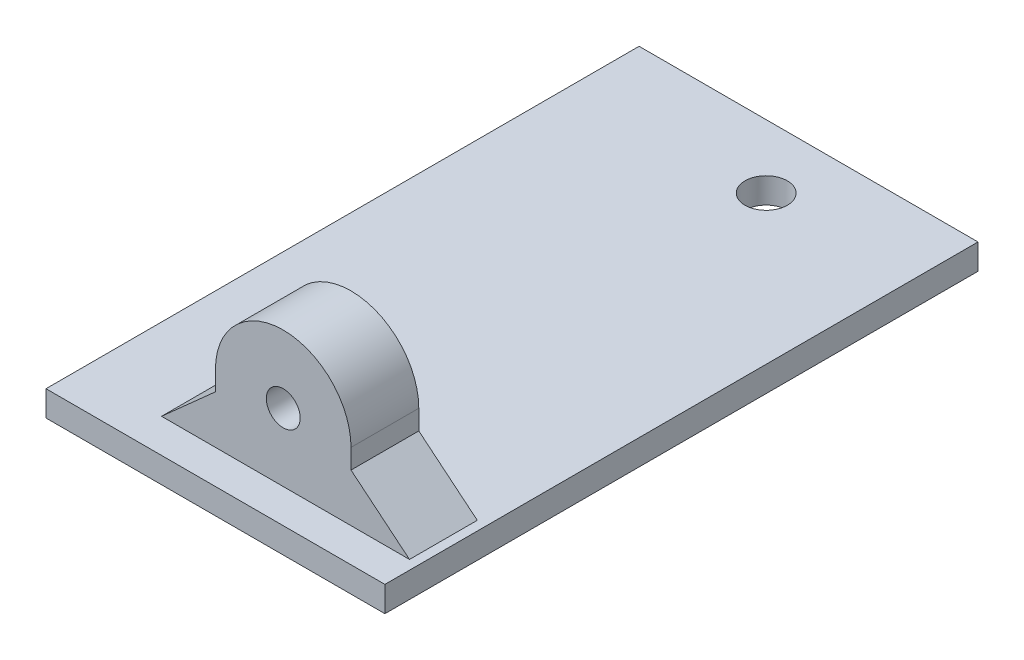
SolidWorks part; units mm, degrees
ref_plane "Front Plane" through (0, 0, 0) normal (0, 0, 1) x (1, 0, 0)
ref_plane "Top Plane" through (0, 0, 0) normal (0, 1, 0) x (1, 0, 0)
ref_plane "Right Plane" through (0, 0, 0) normal (1, 0, 0) x (0, 0, -1)
sketch "Sketch1" plane through (0, 0, 0) normal (0, 1, 0) x (1, 0, 0)
  line L1 (-40, -30) -> (40, -30)
  line L2 (-40, -30) -> (-40, 30)
  line L3 (-40, 30) -> (40, 30)
  line L4 (40, -30) -> (40, 30)
  line L5 (0, 30) -> (0, -30) construction
  line L6 (-40, 0) -> (40, 0) construction
  point P0 (0, 0)
  dimension "D1" = 60
  dimension "D2" = 80
extrude "Boss-Extrude1" add sketch "Sketch1" along normal blind 3
sketch "Sketch3" plane through (0, 3, 0) normal (0, 1, 0) x (1, 0, 0)
  line L1 (-26.5, -22.5) -> (22.5, -22.5)
  line L2 (-26.5, -22.5) -> (-26.5, 22.5)
  line L3 (-26.5, 22.5) -> (22.5, 22.5)
  line L4 (22.5, -22.5) -> (22.5, 22.5)
  line L5 (-2, 22.5) -> (-2, -22.5) construction
  line L6 (-26.5, 0) -> (22.5, 0) construction
  circle A0 centre (-26.5, 22.5) radius 2.5
  circle A1 centre (22.5, 22.5) radius 2.5
  circle A2 centre (22.5, -22.5) radius 2.5
  circle A3 centre (-26.5, -22.5) radius 2.5
  point P9 (-2, 0)
  dimension "D1" = 5
  dimension "D2" = 49
  dimension "D3" = 45
  dimension "D4" = 22.5
extrude "Cut-Extrude1" cut sketch "Sketch3" against normal blind 10 contours L3 A0 L2 | L2 A0 L3 | L4 A1 L3 | L3 A1 L4 | L1 A2 L4 | L4 A2 L1 | L2 A3 L1 | L1 A3 L2 region at (-25.439, 3, 21.439) region at (-26.8537, 3, 22.8537) region at (21.439, 3, 21.439) region at (22.8537, 3, 22.8537) region at (-26.8537, 3, -22.8537) region at (-25.439, 3, -21.439) region at (21.439, 3, -21.439) region at (22.8537, 3, -22.8537)
sketch "Sketch9" plane through (0, 3, 0) normal (0, 1, 0) x (1, 0, 0)
  line L1 (-33, 8.2578) -> (-17, 8.2578)
  line L2 (-33, 8.2578) -> (-33, 0.2578)
  line L3 (-33, 0.2578) -> (-17, 0.2578)
  line L4 (-17, 8.2578) -> (-17, 0.2578)
  line L5 (-25, 0.2578) -> (-25, 8.2578) construction
  line L6 (-33, 4.2578) -> (-17, 4.2578) construction
  point P0 (-25, 4.2578)
  dimension "D1" = 8
  dimension "D2" = 16
  dimension "D4" = 25
extrude "Boss-Extrude3" add sketch "Sketch9" along normal blind 50
sketch "Sketch10" plane through (0, 0, -0.2578) normal (0, 0, 1) x (1, 0, 0)
  line L0 (-33, 53) -> (-17, 53) construction
  line L1 (-33, 53) -> (-33, 3) construction
  line L2 (-17, 53) -> (-17, 3) construction
  line L3 (-33, 45) -> (-33, 53)
  line L4 (-33, 53) -> (-17, 53)
  line L5 (-17, 53) -> (-17, 45)
  circle A0 centre (-25, 45) radius 8
  line M2 (-17, 3) -> (-17, 53)
  line M3 (-17, 53) -> (-33, 53)
  line M4 (-33, 53) -> (-33, 3)
extrude "Cut-Extrude3" cut sketch "Sketch10" against normal blind 50 contours A0 M2 M3 | A0 L4 M4 region at (-31.2131, 51.2131, -0.2578) region at (-18.7869, 51.2131, -0.2578)
sketch "Sketch11" plane through (0, 3, 0) normal (0, 1, 0) x (1, 0, 0)
  line L0 (24, -36) -> (24, -31.3272) construction
  line L1 (16, -28) -> (32, -28)
  line L2 (16, -28) -> (16, -36)
  line L3 (16, -36) -> (32, -36)
  line L4 (32, -28) -> (32, -36)
  line L5 (24, -36) -> (24, -28) construction
  line L6 (16, -32) -> (32, -32) construction
  point P0 (24, -32)
  dimension "D1" = 8
  dimension "D2" = 16
  dimension "D3" = 32
  dimension "D4" = 16
extrude "Boss-Extrude4" add sketch "Sketch11" along normal blind 16 contours L1 L4 L3 L2
sketch "Sketch12" plane through (0, 0, 36) normal (0, 0, 1) x (1, 0, 0)
  line L0 (16, 19) -> (32, 19) construction
  line L1 (16, 11) -> (14, 19)
  line L2 (14, 19) -> (32, 19)
  line L3 (32, 19) -> (32, 11)
  circle A0 centre (24, 11) radius 8
  circle A1 centre (24, 11) radius 2
  point P6 (24, 19)
  line M2 (32, 3) -> (32, 19)
  line M3 (32, 19) -> (16, 19)
  line M4 (16, 19) -> (16, 3)
  dimension "D1" = 16
  dimension "D2" = 4
extrude "Cut-Extrude4" cut sketch "Sketch12" against normal blind 16 contours A0 M2 M3 | A0 L2 M4 | A1 region at (17.7869, 17.2131, 36) region at (30.2131, 17.2131, 36) region at (24, 11, 36)
sketch "Sketch13" plane through (0, 0, 36) normal (0, 0, 1) x (1, 0, 0)
  line L0 (24, 9) -> (24, 30.06) construction
  circle A0 centre (24, 11) radius 2 construction
ref_plane "Plane1" through (24, 0, 0) normal (1, 0, 0) x (0, 0, -1)
split "Split1" trim tools "Right Plane" bodies to split 112 resulting bodies 113 114
move or copy body "Body-Move/Copy1" bodies to move or copy 114 copy no translate (-47.17, 0, 0)
sketch "Sketch14" plane through (0, 0, -0.2578) normal (0, 0, 1) x (1, 0, 0)
  line L0 (-78.4102, 23.6296) -> (-66.1102, 23.6296)
  line L1 (-78.4102, 46.4296) -> (-78.4102, 23.6296)
  line L2 (-66.1102, 46.4296) -> (-78.4102, 46.4296)
  line L3 (-66.1102, 23.6296) -> (-66.1102, 46.4296)
  circle A0 centre (-72.2602, 20.7796) radius 1
  circle A1 centre (-72.2602, 49.2796) radius 1
extrude "Cut-Extrude5" cut sketch "Sketch14" against normal blind 10
sketch "Sketch15" plane through (0, 3, 0) normal (0, 1, 0) x (1, 0, 0)
  line L0 (-54.67, 22.5) -> (-73.67, 22.5) construction
  line L1 (-73.67, -22.5) -> (-54.67, -22.5) construction
  line L2 (-52.17, 22.5) -> (-52.17, 13.6809) construction
  line L3 (-47.17, 30) -> (-47.17, -30) construction
  circle A0 centre (-54.67, 22.5) radius 2.5
  circle A1 centre (-54.67, -22.5) radius 2.5
  circle A2 centre (-73.67, 22.5) radius 2.5 construction
  dimension "D1" = 5
extrude "Cut-Extrude6" cut sketch "Sketch15" against normal blind 10 contours A1 | A0 region at (-54.67, 3, 22.5)
sketch "Sketch17" plane through (0, 0, 30) normal (0, 0, 1) x (1, 0, 0)
  line L6 (16, 3) -> (0, 3)
  line L7 (0, 3) -> (0, 0)
  line L8 (0, 0) -> (40, 0)
  line L9 (40, 0) -> (40, 3)
  line L10 (40, 3) -> (32, 3)
  line L11 (32, 3) -> (16, 3)
  line L12 (16, 3) -> (0, 3)
  line L13 (0, 3) -> (0, 0)
  line L14 (0, 0) -> (40, 0)
  line L15 (40, 0) -> (40, 3)
  line L16 (40, 3) -> (32, 3)
  line L17 (32, 3) -> (16, 3)
  dimension "D1" = 0
extrude "Boss-Extrude6" add sketch "Sketch17" along normal blind 10
sketch "Sketch18" plane through (0, 0, 36) normal (0, 0, 1) x (1, 0, 0)
  line L0 (16, 8.682) -> (9.6381, 3)
  line L1 (16, 11) -> (16, 3) construction
  line L2 (40, 3) -> (0, 3) construction
  line L3 (9.6381, 3) -> (16, 3)
  line L4 (32, 8.682) -> (38.9012, 3)
  line L5 (32, 11) -> (32, 3) construction
  line L6 (38.9012, 3) -> (32, 3)
  line L7 (32, 3) -> (32, 8.682)
  line M3 (16, 11) -> (16, 3)
extrude "Boss-Extrude7" add sketch "Sketch18" against normal up to surface (8 mm away) contours L0 L3 M3 | L4 L6 L7 region at (13.8794, 4.894, 36) up to face at (22, 11, 28)
sketch "Sketch19" plane through (0, 3, 0) normal (0, 1, 0) x (1, 0, 0)
  line L0 (-54.67, 22.5) -> (22.5, 22.5) construction
  dimension "D1" = 77.17
sketch "Sketch20" plane through (0, 3, 0) normal (0, 1, 0) x (1, 0, 0)
  line L0 (0, 30) -> (0, -9.2379) construction
  line L1 (0, 30) -> (0, -40) construction
  line L2 (-47.17, 30) -> (-47.17, 5.4464) construction
  line L3 (-47.17, 30) -> (-47.17, -30) construction
sketch "Sketch21" plane through (0, 0, 0) normal (0, 0, 1) x (1, 0, 0)
  line L1 (-109.9881, -8.2212) -> (-28.2252, -8.2212)
  line L2 (-109.9881, -8.2212) -> (-109.9881, 57.8611)
  line L3 (-109.9881, 57.8611) -> (-28.2252, 57.8611)
  line L4 (-28.2252, -8.2212) -> (-28.2252, 57.8611)
extrude "Cut-Extrude7" cut sketch "Sketch21" against normal mid plane 80
